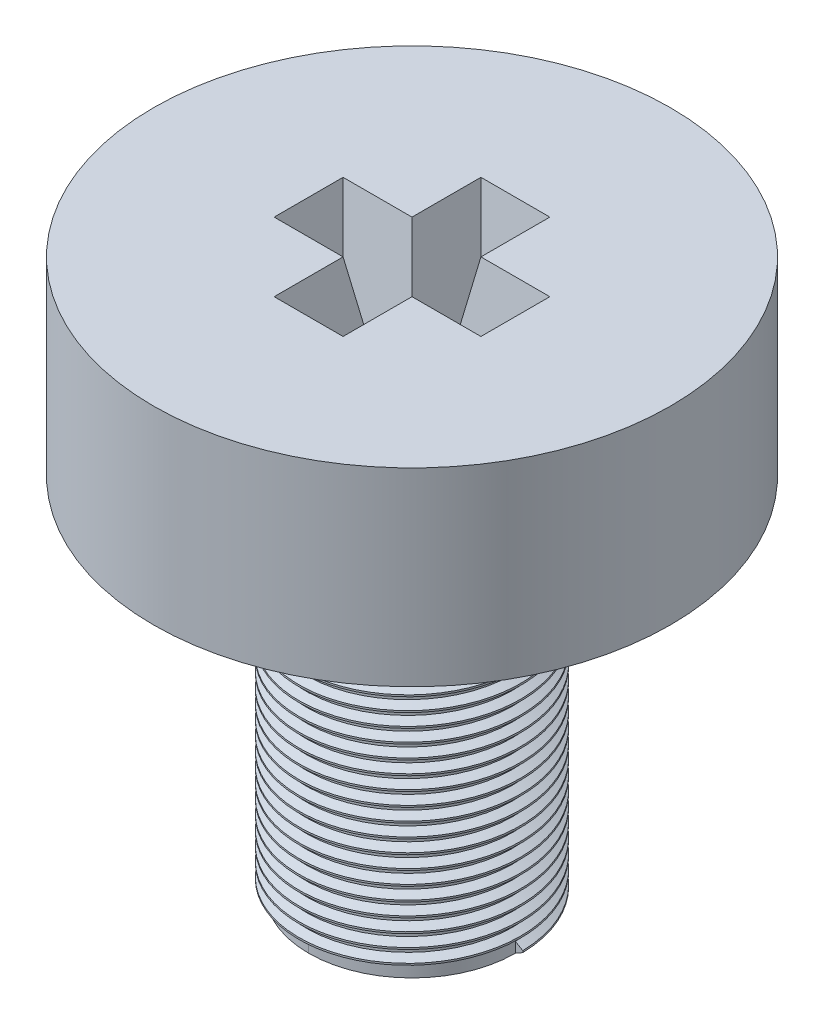
SolidWorks part; units mm, degrees
ref_plane "前视基准面" through (0, 0, 0) normal (0, 0, 1) x (1, 0, 0)
ref_plane "上视基准面" through (0, 0, 0) normal (0, 1, 0) x (1, 0, 0)
ref_plane "右视基准面" through (0, 0, 0) normal (1, 0, 0) x (0, 0, -1)
other "Configuration Table"
sketch "草图1" plane through (0, 0, 0) normal (0, 0, 1) x (1, 0, 0)
  line L0 (0, 53.1536) -> (0, -45.2352) construction
  line L1 (0, 32) -> (15, 32)
  line L2 (15, 32) -> (15, 21)
  line L3 (15, 21) -> (6, 21)
  line L4 (6, 21) -> (6, 0)
  line L5 (6, 0) -> (0, 0)
  line L6 (0, 32) -> (0, 0)
  dimension "D1" = 32
  dimension "D2" = 6
  dimension "D3" = 15
  dimension "D4" = 11
revolve "旋转1" add sketch "草图1" angle 360 about L0
thread "螺纹线1" pitch 0.7937 method extrude profile "螺纹线轮廓2" start angle 0, offset 0, length 20, pitch 0.7937, diameter 12
ref_plane "基准面3" through (6, 0, 0) normal (0, 0, 1) x (1, 0, 0)
sketch "螺纹线轮廓2" plane through (6, 0, 0) normal (0, 0, 1) x (1, 0, 0)
  line L0 (0, 0) -> (0, 0.7937) construction
  line L1 (0, 0) -> (0.4296, 0.248)
  line L2 (0.4296, 0.248) -> (0.4296, 0.3473)
  line L3 (0.4296, 0.3473) -> (0, 0.5953)
  line L4 (0.4296, 0.2977) -> (0, 0.2977) construction
  line L11 (0, 0) -> (0, 0.5953)
  point P2 (0, 0)
  dimension "Pitch" = 0.7937
  dimension "Profile_Angle" = 60
  dimension "Profile_Land" = 0.0992
  dimension "Profile_Height" = 0.4296
sketch "草图7" plane through (0, 32, 0) normal (0, 1, 0) x (1, 0, 0)
  line L0 (0, 7.778) -> (0, -7.6157) construction
  line L1 (-10.4699, 0) -> (9.9829, 0) construction
  line L2 (-2, 6) -> (2, 6)
  line L3 (2, 6) -> (2, 2)
  line L4 (2, 2) -> (6, 2)
  line L5 (6, 2) -> (6, -2)
  line L6 (2, -2) -> (6, -2)
  line L7 (2, -6) -> (2, -2)
  line L8 (-2, -6) -> (2, -6)
  line L9 (-2, -6) -> (-2, -2)
  line L10 (-2, -2) -> (-6, -2)
  line L11 (-6, 2) -> (-6, -2)
  line L12 (-2, 2) -> (-6, 2)
  line L13 (-2, 6) -> (-2, 2)
  point P5 (-6, 0)
  point P11 (6, 0)
  point P15 (0, -6)
  point P20 (0, 6)
  dimension "D1" = 4
  dimension "D2" = 2
extrude "切除-拉伸1" cut sketch "草图7" against normal blind 7 draft 10
